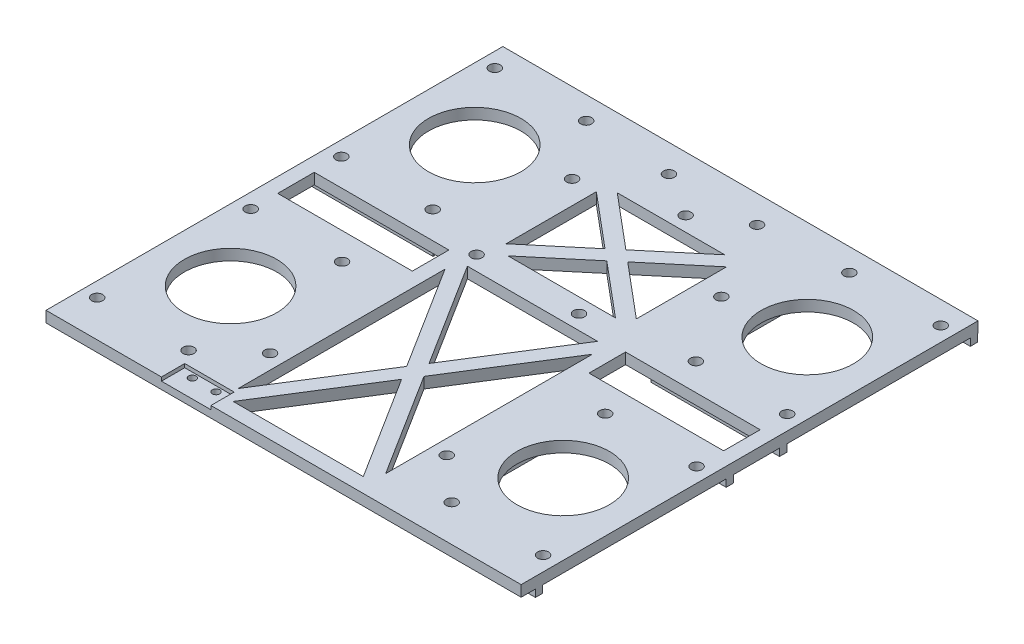
SolidWorks part; units mm, degrees
ref_plane "Front Plane" through (0, 0, 0) normal (0, 0, 1) x (1, 0, 0)
ref_plane "Top Plane" through (0, 0, 0) normal (0, 1, 0) x (1, 0, 0)
ref_plane "Right Plane" through (0, 0, 0) normal (1, 0, 0) x (0, 0, -1)
sketch "Sketch1" plane through (0, 0, 0) normal (0, 1, 0) x (1, 0, 0)
  line L1 (-65, 62.5) -> (65, 62.5)
  line L2 (-65, 62.5) -> (-65, -62.5)
  line L3 (-65, -62.5) -> (65, -62.5)
  line L4 (65, 62.5) -> (65, -62.5)
  line L5 (-65, 62.5) -> (65, -62.5) construction
  line L6 (-65, -62.5) -> (65, 62.5) construction
  point P0 (0, 0)
  dimension "D1" = 130
  dimension "D2" = 125
extrude "Boss-Extrude1" add sketch "Sketch1" along normal blind 5
sketch "Sketch2" plane through (0, 5, 0) normal (0, 1, 0) x (1, 0, 0)
  line L1 (-65, -62.5) -> (65, -62.5) construction
  line L2 (-65, 62.5) -> (-65, -62.5) construction
  circle A0 centre (-61, -52.5) radius 1.5
  circle A1 centre (-36, -52.5) radius 1.5
  circle A2 centre (-36, -10.5) radius 1.5
  circle A3 centre (-61, -10.5) radius 1.5
  circle A4 centre (-45.5, -31.5) radius 12.65
  dimension "D2" = 25.3
  dimension "D7" = 3
  dimension "D8" = 3
  dimension "D9" = 3
  dimension "D10" = 3
  dimension "D1" = 19.5
  dimension "D3" = 31
  dimension "D4" = 4
  dimension "D5" = 10
  dimension "D6" = 10
  dimension "D11" = 4
  dimension "D12" = 42
  dimension "D13" = 42
  dimension "D14" = 25
  dimension "D15" = 25
extrude "Cut-Extrude1" cut sketch "Sketch2" against normal blind 10
ref_plane "Plane1" through (0, 0, 0) normal (-1, 0, 0) x (0, 0, 1)
ref_plane "Plane2" through (0, 0, 0) normal (0, 0, 1) x (1, 0, 0)
mirror "Mirror3" about plane through (0, 0, 0) normal (-1, 0, 0) of "Cut-Extrude1"
sketch "Sketch4" plane through (0, 5, 0) normal (0, 1, 0) x (1, 0, 0)
  line L0 (0, 62.5) -> (0, 47.5) construction
  line L1 (65, 62.5) -> (-65, 62.5) construction
  line L2 (-12.0498, 55) -> (12.0498, 55) construction
  circle A0 centre (0, 47.5) radius 1.5
  circle A1 centre (12.0498, 55) radius 1.5
  circle A2 centre (-12.0498, 55) radius 1.5
  point P9 (0, 55)
  dimension "D2" = 3
  dimension "D3" = 3
  dimension "D4" = 3
  dimension "D1" = 15
  dimension "D5" = 24.0996
extrude "Cut-Extrude3" cut sketch "Sketch4" against normal blind 10
sketch "Sketch5" plane through (0, 0, 0) normal (0, -1, 0) x (1, 0, 0)
  line L0 (-58.15, 31.5) -> (-65, 31.5) construction
  line L1 (-65, -62.5) -> (-65, 62.5) construction
  line L2 (-65, 56.6) -> (-65, 6.4)
  line L3 (-65, 56.6) -> (-31.8, 56.6)
  line L4 (-31.8, 56.6) -> (-31.8, 6.4)
  line L5 (-31.8, 6.4) -> (-65, 6.4)
  line L6 (-65, 58.6) -> (-29.8, 58.6)
  line L7 (-29.8, 58.6) -> (-29.8, 4.4)
  line L8 (-29.8, 4.4) -> (-65, 4.4)
  line L9 (-65, 4.4) -> (-65, 6.4)
  line L10 (-65, 58.6) -> (-65, 56.6)
  circle A0 centre (-45.5, 31.5) radius 12.65 construction
  point P10 (-65, 31.5)
  line M39 (-65, 62.5) -> (-65, -62.5)
  dimension "D1" = 50.2
  dimension "D2" = 33.2
  dimension "D3" = 2
  dimension "D4" = 2
  dimension "D5" = 2
extrude "Boss-Extrude2" add sketch "Sketch5" along normal blind 2 contours L8 L7 L6 L3 L4 L5 M39 region at (-64.3537, 0, 57.6)
mirror "Mirror5" about plane through (0, 0, 0) normal (-1, 0, 0) of "Boss-Extrude2"
ref_plane "Plane3" through (0, 0, 0) normal (0, 0, 1) x (1, 0, 0)
ref_plane "Plane4" through (0, 0, -1.9) normal (0, 0, 1) x (1, 0, 0)
mirror "Mirror7" about plane through (0, 0, -1.9) normal (0, 0, 1) of "Mirror5", "Boss-Extrude2", "Mirror3"
ref_plane "Plane5" through (0, 0, 0) normal (0, -1, 0) x (-1, 0, 0)
sketch "Sketch10" plane through (0, 0, 0) normal (0, -1, 0) x (-1, 0, 0)
  circle A0 centre (-24.17, -42.03) radius 1.5
  circle A1 centre (24.17, -42.03) radius 1.5
  circle A2 centre (-8.73, 9.6) radius 1.5
  circle A3 centre (19.29, 9.6) radius 1.5
  circle A4 centre (-24.17, 33.11) radius 1.5
  circle A5 centre (24.17, 40.6) radius 1.5
  dimension "D1" = 3
  dimension "D6" = 3
  dimension "D7" = 3
  dimension "D10" = 3
  dimension "D11" = 3
  dimension "D12" = 3
extrude "Cut-Extrude8" cut sketch "Sketch10" against normal through all
sketch "Sketch11" plane through (0, 0, 0) normal (0, -1, 0) x (1, 0, 0)
  circle A0 centre (-12.0498, -55) radius 2.65
  circle A1 centre (0, -47.5) radius 2.65
  circle A2 centre (12.0498, -55) radius 2.65
  circle A3 centre (-24.17, -40.6) radius 2.65
  circle A4 centre (24.17, -33.11) radius 2.65
  circle A5 centre (8.73, -9.6) radius 2.65
  circle A6 centre (-19.29, -9.6) radius 2.65
  circle A7 centre (-24.17, 42.03) radius 2.65
  circle A8 centre (24.17, 42.03) radius 2.65
  circle A9 centre (-61, -14.3) radius 2.65
  circle A10 centre (-36, -14.3) radius 2.65
  circle A11 centre (-61, -56.3) radius 2.65
  circle A12 centre (-36, -56.3) radius 2.65
  circle A13 centre (36, -56.3) radius 2.65
  circle A14 centre (61, -56.3) radius 2.65
  circle A15 centre (36, -14.3) radius 2.65
  circle A16 centre (61, -14.3) radius 2.65
  circle A17 centre (36, 10.5) radius 2.65
  circle A18 centre (61, 10.5) radius 2.65
  circle A19 centre (61, 52.5) radius 2.65
  circle A20 centre (36, 52.5) radius 2.65
  circle A21 centre (-36, 52.5) radius 2.65
  circle A22 centre (-36, 10.5) radius 2.65
  circle A23 centre (-61, 10.5) radius 2.65
  circle A24 centre (-61, 52.5) radius 2.65
  dimension "D1" = 5.3
  dimension "D2" = 5.3
  dimension "D3" = 5.3
  dimension "D4" = 5.3
  dimension "D5" = 5.3
  dimension "D6" = 5.3
  dimension "D7" = 5.3
  dimension "D8" = 5.3
  dimension "D9" = 5.3
  dimension "D10" = 5.3
  dimension "D11" = 5.3
  dimension "D12" = 5.3
  dimension "D13" = 5.3
  dimension "D14" = 5.3
  dimension "D15" = 5.3
  dimension "D16" = 5.3
  dimension "D17" = 5.3
  dimension "D18" = 5.3
  dimension "D19" = 5.3
  dimension "D20" = 5.3
  dimension "D21" = 5.3
  dimension "D22" = 5.3
  dimension "D23" = 5.3
  dimension "D24" = 5.3
  dimension "D25" = 5.3
extrude "Cut-Extrude9" cut sketch "Sketch11" against normal blind 0.5
sketch "Sketch12" plane through (0, 5, 0) normal (0, 1, 0) x (1, 0, 0)
  line L0 (-65, -62.5) -> (65, -62.5) construction
  line L1 (-20.17, 5.6) -> (20.17, 5.6)
  line L2 (-20.17, 5.6) -> (-20.17, -58.5)
  line L3 (-20.17, -58.5) -> (20.17, -58.5)
  line L4 (20.17, 5.6) -> (20.17, -58.5)
  line L5 (-20.17, 5.6) -> (20.17, -58.5) construction
  line L6 (-20.17, -58.5) -> (20.17, 5.6) construction
  line L7 (-17.8069, 5.6) -> (0, -22.6951)
  line L8 (20.17, -54.7451) -> (2.3631, -26.45)
  line L9 (2.3631, -26.45) -> (20.17, 1.8451)
  line L10 (0, -22.6951) -> (17.8069, 5.6)
  line L11 (-20.17, 1.8451) -> (-2.3631, -26.45)
  line L12 (-2.3631, -26.45) -> (-20.17, -54.7451)
  line L13 (-17.8069, -58.5) -> (0, -30.2049)
  line L14 (0, -30.2049) -> (17.8069, -58.5)
  circle A0 centre (-19.29, 9.6) radius 1.5 construction
  circle A1 centre (-24.17, -42.03) radius 1.5 construction
  circle A2 centre (24.17, -42.03) radius 1.5 construction
  dimension "D2" = 4
  dimension "D3" = 4
  dimension "D1" = 4
  dimension "D4" = 4
  dimension "D5" = 2
  dimension "D6" = 2
  dimension "D7" = 2
  dimension "D8" = 2
extrude "Cut-Extrude10" cut sketch "Sketch12" against normal through all contours L12 L11 L2 | L7 L10 L1 | L9 L8 L4 | L14 L13 L3 region at (0, 5, 3.8317) region at (-14.2344, 5, 26.45) region at (14.2344, 5, 26.45) region at (0, 5, 49.0683)
sketch "Sketch13" plane through (0, 5, 0) normal (0, 1, 0) x (1, 0, 0)
  line L0 (-61, 14.3) -> (-61, -10.5) construction
  line L1 (-61, 1.9) -> (-61, -3.1)
  line L2 (-61, -3.1) -> (-24.17, -3.1)
  line L3 (-24.17, -3.1) -> (-24.17, 6.9)
  line L4 (-24.17, 6.9) -> (-61, 6.9)
  line L5 (-61, 6.9) -> (-61, 1.9)
  line L6 (-20.17, 1.8451) -> (-20.17, -54.7451) construction
  dimension "D1" = 10
  dimension "D2" = 5
  dimension "D3" = 4
extrude "Cut-Extrude11" cut sketch "Sketch13" against normal through all
mirror "Mirror9" about plane through (0, 0, 0) normal (-1, 0, 0) of "Cut-Extrude11"
sketch "Sketch14" plane through (0, 5, 0) normal (0, 1, 0) x (1, 0, 0)
  line L0 (-17.8069, 43.5) -> (17.8069, 13.6) construction
  line L1 (-17.8069, 43.5) -> (17.8069, 43.5)
  line L2 (-17.8069, 43.5) -> (-17.8069, 13.6)
  line L3 (-17.8069, 13.6) -> (17.8069, 13.6)
  line L4 (17.8069, 43.5) -> (17.8069, 13.6)
  line L5 (-17.8069, 13.6) -> (17.8069, 43.5) construction
  line L6 (-17.8069, 40.8886) -> (-3.1104, 28.55)
  line L7 (-3.1104, 28.55) -> (-17.8069, 16.2114)
  line L8 (-14.6965, 13.6) -> (0, 25.9386)
  line L9 (0, 25.9386) -> (14.6965, 13.6)
  line L10 (17.8069, 16.2114) -> (3.1104, 28.55)
  line L11 (3.1104, 28.55) -> (17.8069, 40.8886)
  line L12 (14.6965, 43.5) -> (0, 31.1614)
  line L13 (0, 31.1614) -> (-14.6965, 43.5)
  circle A0 centre (0, 47.5) radius 1.5 construction
  circle A1 centre (8.73, 9.6) radius 1.5 construction
  dimension "D1" = 4
  dimension "D2" = 4
  dimension "D3" = 2
  dimension "D4" = 2
  dimension "D5" = 2
  dimension "D6" = 2
  dimension "D7" = 2
  dimension "D8" = 2
  dimension "D9" = 2
  dimension "D10" = 2
extrude "Cut-Extrude12" cut sketch "Sketch14" against normal through all contours L7 L6 L2 | L13 L12 L1 | L11 L10 L4 | L9 L8 L3 region at (0, 5, -39.3871) region at (-12.9081, 5, -28.55) region at (12.9081, 5, -28.55) region at (0, 5, -17.7129)
sketch "Sketch15" plane through (0, 5, 0) normal (0, 1, 0) x (1, 0, 0)
  line L1 (-63.5, 58.8) -> (-58.5, 58.8)
  line L2 (-63.5, 58.8) -> (-63.5, 53.8)
  line L3 (-63.5, 53.8) -> (-58.5, 53.8)
  line L4 (65, -62.5) -> (65, 62.5)
  line L5 (65, 62.5) -> (-65, 62.5)
  line L6 (-65, 62.5) -> (-65, -62.5)
  line L7 (-65, -62.5) -> (65, -62.5)
  line L8 (65, -62.5) -> (65, 62.5)
  line L9 (65, 62.5) -> (-65, 62.5)
  line L10 (-65, 62.5) -> (-65, -62.5)
  line L11 (-65, -62.5) -> (65, -62.5)
  line L12 (-58.5, 58.8) -> (-58.5, 53.8)
  line L13 (-63.5, 58.8) -> (-58.5, 53.8) construction
  line L14 (-63.5, 53.8) -> (-58.5, 58.8) construction
  line L15 (-38.5, 58.8) -> (-33.5, 58.8)
  line L16 (-38.5, 58.8) -> (-38.5, 53.8)
  line L17 (-38.5, 53.8) -> (-33.5, 53.8)
  line L18 (-33.5, 58.8) -> (-33.5, 53.8)
  line L19 (-38.5, 58.8) -> (-33.5, 53.8) construction
  line L20 (-38.5, 53.8) -> (-33.5, 58.8) construction
  line L21 (-14.5498, 57.5) -> (-9.5498, 57.5)
  line L22 (-14.5498, 57.5) -> (-14.5498, 52.5)
  line L23 (-14.5498, 52.5) -> (-9.5498, 52.5)
  line L24 (-9.5498, 57.5) -> (-9.5498, 52.5)
  line L25 (-14.5498, 57.5) -> (-9.5498, 52.5) construction
  line L26 (-14.5498, 52.5) -> (-9.5498, 57.5) construction
  line L27 (-2.5, 50) -> (2.5, 50)
  line L28 (-2.5, 50) -> (-2.5, 45)
  line L29 (-2.5, 45) -> (2.5, 45)
  line L30 (2.5, 50) -> (2.5, 45)
  line L31 (-2.5, 50) -> (2.5, 45) construction
  line L32 (-2.5, 45) -> (2.5, 50) construction
  line L33 (9.5498, 57.5) -> (14.5498, 57.5)
  line L34 (9.5498, 57.5) -> (9.5498, 52.5)
  line L35 (9.5498, 52.5) -> (14.5498, 52.5)
  line L36 (14.5498, 57.5) -> (14.5498, 52.5)
  line L37 (9.5498, 57.5) -> (14.5498, 52.5) construction
  line L38 (9.5498, 52.5) -> (14.5498, 57.5) construction
  line L39 (33.5, 58.8) -> (38.5, 58.8)
  line L40 (33.5, 58.8) -> (33.5, 53.8)
  line L41 (33.5, 53.8) -> (38.5, 53.8)
  line L42 (38.5, 58.8) -> (38.5, 53.8)
  line L43 (33.5, 58.8) -> (38.5, 53.8) construction
  line L44 (33.5, 53.8) -> (38.5, 58.8) construction
  line L45 (63.5, 58.8) -> (58.5, 58.8)
  line L46 (63.5, 58.8) -> (63.5, 53.8)
  line L47 (63.5, 53.8) -> (58.5, 53.8)
  line L48 (58.5, 58.8) -> (58.5, 53.8)
  line L49 (63.5, 58.8) -> (58.5, 53.8) construction
  line L50 (63.5, 53.8) -> (58.5, 58.8) construction
  line L51 (33.5, 16.8) -> (38.5, 16.8)
  line L52 (33.5, 16.8) -> (33.5, 11.8)
  line L53 (33.5, 11.8) -> (38.5, 11.8)
  line L54 (38.5, 16.8) -> (38.5, 11.8)
  line L55 (33.5, 16.8) -> (38.5, 11.8) construction
  line L56 (33.5, 11.8) -> (38.5, 16.8) construction
  line L57 (63.5, 16.8) -> (58.5, 16.8)
  line L58 (63.5, 16.8) -> (63.5, 11.8)
  line L59 (63.5, 11.8) -> (58.5, 11.8)
  line L60 (58.5, 16.8) -> (58.5, 11.8)
  line L61 (63.5, 16.8) -> (58.5, 11.8) construction
  line L62 (63.5, 11.8) -> (58.5, 16.8) construction
  line L63 (21.67, 35.61) -> (26.67, 35.61)
  line L64 (21.67, 35.61) -> (21.67, 30.61)
  line L65 (21.67, 30.61) -> (26.67, 30.61)
  line L66 (26.67, 35.61) -> (26.67, 30.61)
  line L67 (21.67, 35.61) -> (26.67, 30.61) construction
  line L68 (21.67, 30.61) -> (26.67, 35.61) construction
  line L69 (33.5, -8) -> (38.5, -8)
  line L70 (33.5, -8) -> (33.5, -13)
  line L71 (33.5, -13) -> (38.5, -13)
  line L72 (38.5, -8) -> (38.5, -13)
  line L73 (33.5, -8) -> (38.5, -13) construction
  line L74 (33.5, -13) -> (38.5, -8) construction
  line L75 (63.5, -8) -> (58.5, -8)
  line L76 (63.5, -8) -> (63.5, -13)
  line L77 (63.5, -13) -> (58.5, -13)
  line L78 (58.5, -8) -> (58.5, -13)
  line L79 (63.5, -8) -> (58.5, -13) construction
  line L80 (63.5, -13) -> (58.5, -8) construction
  line L81 (21.67, -39.53) -> (26.67, -39.53)
  line L82 (21.67, -39.53) -> (21.67, -44.53)
  line L83 (21.67, -44.53) -> (26.67, -44.53)
  line L84 (26.67, -39.53) -> (26.67, -44.53)
  line L85 (21.67, -39.53) -> (26.67, -44.53) construction
  line L86 (21.67, -44.53) -> (26.67, -39.53) construction
  line L87 (38.5, -50) -> (33.5, -50)
  line L88 (38.5, -50) -> (38.5, -55)
  line L89 (38.5, -55) -> (33.5, -55)
  line L90 (33.5, -50) -> (33.5, -55)
  line L91 (38.5, -50) -> (33.5, -55) construction
  line L92 (38.5, -55) -> (33.5, -50) construction
  line L93 (63.5, -50) -> (58.5, -50)
  line L94 (63.5, -50) -> (63.5, -55)
  line L95 (63.5, -55) -> (58.5, -55)
  line L96 (58.5, -50) -> (58.5, -55)
  line L97 (63.5, -50) -> (58.5, -55) construction
  line L98 (63.5, -55) -> (58.5, -50) construction
  line L99 (-26.67, -39.53) -> (-21.67, -39.53)
  line L100 (-26.67, -39.53) -> (-26.67, -44.53)
  line L101 (-26.67, -44.53) -> (-21.67, -44.53)
  line L102 (-21.67, -39.53) -> (-21.67, -44.53)
  line L103 (-26.67, -39.53) -> (-21.67, -44.53) construction
  line L104 (-26.67, -44.53) -> (-21.67, -39.53) construction
  line L105 (-38.5, -50) -> (-33.5, -50)
  line L106 (-38.5, -50) -> (-38.5, -55)
  line L107 (-38.5, -55) -> (-33.5, -55)
  line L108 (-33.5, -50) -> (-33.5, -55)
  line L109 (-38.5, -50) -> (-33.5, -55) construction
  line L110 (-38.5, -55) -> (-33.5, -50) construction
  line L111 (-38.5, -8) -> (-33.5, -8)
  line L112 (-38.5, -8) -> (-38.5, -13)
  line L113 (-38.5, -13) -> (-33.5, -13)
  line L114 (-33.5, -8) -> (-33.5, -13)
  line L115 (-38.5, -8) -> (-33.5, -13) construction
  line L116 (-38.5, -13) -> (-33.5, -8) construction
  line L117 (6.23, 12.1) -> (11.23, 12.1)
  line L118 (6.23, 12.1) -> (6.23, 7.1)
  line L119 (6.23, 7.1) -> (11.23, 7.1)
  line L120 (11.23, 12.1) -> (11.23, 7.1)
  line L121 (6.23, 12.1) -> (11.23, 7.1) construction
  line L122 (6.23, 7.1) -> (11.23, 12.1) construction
  line L123 (-21.79, 12.1) -> (-16.79, 12.1)
  line L124 (-21.79, 12.1) -> (-21.79, 7.1)
  line L125 (-21.79, 7.1) -> (-16.79, 7.1)
  line L126 (-16.79, 12.1) -> (-16.79, 7.1)
  line L127 (-21.79, 12.1) -> (-16.79, 7.1) construction
  line L128 (-21.79, 7.1) -> (-16.79, 12.1) construction
  line L129 (-26.67, 43.1) -> (-21.67, 43.1)
  line L130 (-26.67, 43.1) -> (-26.67, 38.1)
  line L131 (-26.67, 38.1) -> (-21.67, 38.1)
  line L132 (-21.67, 43.1) -> (-21.67, 38.1)
  line L133 (-26.67, 43.1) -> (-21.67, 38.1) construction
  line L134 (-26.67, 38.1) -> (-21.67, 43.1) construction
  line L135 (-63.5, 16.8) -> (-58.5, 16.8)
  line L136 (-63.5, 16.8) -> (-63.5, 11.8)
  line L137 (-63.5, 11.8) -> (-58.5, 11.8)
  line L138 (-58.5, 16.8) -> (-58.5, 11.8)
  line L139 (-63.5, 16.8) -> (-58.5, 11.8) construction
  line L140 (-63.5, 11.8) -> (-58.5, 16.8) construction
  line L141 (-38.5, 16.8) -> (-33.5, 16.8)
  line L142 (-38.5, 16.8) -> (-38.5, 11.8)
  line L143 (-38.5, 11.8) -> (-33.5, 11.8)
  line L144 (-33.5, 16.8) -> (-33.5, 11.8)
  line L145 (-38.5, 16.8) -> (-33.5, 11.8) construction
  line L146 (-38.5, 11.8) -> (-33.5, 16.8) construction
  line L147 (-63.5, -8) -> (-58.5, -8)
  line L148 (-63.5, -8) -> (-63.5, -13)
  line L149 (-63.5, -13) -> (-58.5, -13)
  line L150 (-58.5, -8) -> (-58.5, -13)
  line L151 (-63.5, -8) -> (-58.5, -13) construction
  line L152 (-63.5, -13) -> (-58.5, -8) construction
  line L153 (-63.5, -50) -> (-58.5, -50)
  line L154 (-63.5, -50) -> (-63.5, -55)
  line L155 (-63.5, -55) -> (-58.5, -55)
  line L156 (-58.5, -50) -> (-58.5, -55)
  line L157 (-63.5, -50) -> (-58.5, -55) construction
  line L158 (-63.5, -55) -> (-58.5, -50) construction
  circle A0 centre (-61, 56.3) radius 1.5 construction
  circle A1 centre (-36, 56.3) radius 1.5 construction
  circle A2 centre (-12.0498, 55) radius 1.5 construction
  circle A3 centre (0, 47.5) radius 1.5 construction
  circle A4 centre (12.0498, 55) radius 1.5 construction
  circle A5 centre (36, 56.3) radius 1.5 construction
  circle A6 centre (61, 56.3) radius 1.5 construction
  circle A7 centre (24.17, 33.11) radius 1.5 construction
  circle A8 centre (36, 14.3) radius 1.5 construction
  circle A9 centre (61, 14.3) radius 1.5 construction
  circle A10 centre (-24.17, 40.6) radius 1.5 construction
  circle A11 centre (-61, 14.3) radius 1.5 construction
  circle A12 centre (-36, 14.3) radius 1.5 construction
  circle A13 centre (-19.29, 9.6) radius 1.5 construction
  circle A14 centre (8.73, 9.6) radius 1.5 construction
  circle A15 centre (-61, -10.5) radius 1.5 construction
  circle A16 centre (-36, -10.5) radius 1.5 construction
  circle A17 centre (36, -10.5) radius 1.5 construction
  circle A18 centre (61, -10.5) radius 1.5 construction
  circle A19 centre (61, -52.5) radius 1.5 construction
  circle A20 centre (36, -52.5) radius 1.5 construction
  circle A21 centre (24.17, -42.03) radius 1.5 construction
  circle A22 centre (-24.17, -42.03) radius 1.5 construction
  circle A23 centre (-36, -52.5) radius 1.5 construction
  circle A24 centre (-61, -52.5) radius 1.5 construction
  point P2 (-61, 56.3)
  point P12 (-36, 56.3)
  point P20 (-12.0498, 55)
  point P26 (0, 47.5)
  point P32 (12.0498, 55)
  point P38 (36, 56.3)
  point P44 (61, 56.3)
  point P50 (36, 14.3)
  point P56 (61, 14.3)
  point P62 (24.17, 33.11)
  point P84 (36, -10.5)
  point P90 (61, -10.5)
  point P96 (24.17, -42.03)
  point P102 (36, -52.5)
  point P108 (61, -52.5)
  point P114 (-24.17, -42.03)
  point P120 (-36, -52.5)
  point P126 (-36, -10.5)
  point P132 (8.73, 9.6)
  point P138 (-19.29, 9.6)
  point P144 (-24.17, 40.6)
  point P150 (-61, 14.3)
  point P156 (-36, 14.3)
  point P162 (-61, -10.5)
  point P168 (-61, -52.5)
  dimension "D2" = 2.5
  dimension "D3" = 2.5
  dimension "D4" = 2.5
  dimension "D5" = 2.5
  dimension "D6" = 2.5
  dimension "D7" = 2.5
  dimension "D8" = 2.5
  dimension "D9" = 2.5
  dimension "D10" = 2.5
  dimension "D11" = 2.5
  dimension "D12" = 2.5
  dimension "D13" = 2.5
  dimension "D15" = 2.5
  dimension "D16" = 2.5
  dimension "D17" = 2.5
  dimension "D18" = 2.5
  dimension "D19" = 2.5
  dimension "D20" = 2.5
  dimension "D21" = 2.5
  dimension "D22" = 2.5
  dimension "D23" = 2.5
  dimension "D24" = 2.5
  dimension "D25" = 2.5
  dimension "D26" = 2.5
  dimension "D27" = 2.5
  dimension "D28" = 2.5
  dimension "D29" = 2.5
  dimension "D30" = 2.5
  dimension "D31" = 2.5
  dimension "D32" = 2.5
  dimension "D33" = 2.5
  dimension "D34" = 2.5
  dimension "D35" = 2.5
  dimension "D36" = 2.5
  dimension "D37" = 2.5
  dimension "D38" = 2.5
  dimension "D39" = 2.5
  dimension "D40" = 2.5
  dimension "D41" = 2.5
  dimension "D42" = 2.5
  dimension "D43" = 2.5
  dimension "D44" = 2.5
  dimension "D45" = 2.5
  dimension "D46" = 2.5
  dimension "D47" = 2.5
  dimension "D48" = 2.5
  dimension "D49" = 2.5
  dimension "D14" = 2.5
  dimension "D1" = 0
extrude "Cut-Extrude14" cut sketch "Sketch15" against normal blind 2
ref_plane "Plane6" through (0, 13, 0) normal (0, 1, 0) x (1, 0, 0)
sketch "Sketch17" plane through (0, 13, 0) normal (0, 1, 0) x (1, 0, 0)
  line L1 (-68.0587, 64.2777) -> (69.5711, 64.2777)
  line L2 (-68.0587, 64.2777) -> (-68.0587, -66.7984)
  line L3 (-68.0587, -66.7984) -> (69.5711, -66.7984)
  line L4 (69.5711, 64.2777) -> (69.5711, -66.7984)
extrude "Cut-Extrude15" cut sketch "Sketch17" against normal blind 2 from surface starting at face at (-61, 5, -15.8)
sketch "Sketch18" plane through (0, 3, 0) normal (0, 1, 0) x (1, 0, 0)
  line L0 (-65, -62.5) -> (65, -62.5) construction
  line L1 (-33.412, -56.1297) -> (-19.8846, -56.1297)
  line L2 (-33.412, -56.1297) -> (-33.412, -62.5)
  line L3 (-33.412, -62.5) -> (-19.8846, -62.5)
  line L4 (-19.8846, -56.1297) -> (-19.8846, -62.5)
extrude "Cut-Extrude16" cut sketch "Sketch18" against normal blind 1
sketch "Sketch19" plane through (0, 2, 0) normal (0, 1, 0) x (1, 0, 0)
  circle A0 centre (-23.4201, -57.55) radius 1
  circle A1 centre (-29.9201, -57.55) radius 1
extrude "Cut-Extrude17" cut sketch "Sketch19" against normal blind 5
sketch "Sketch20" plane through (0, 0, 0) normal (0, -1, 0) x (1, 0, 0)
  line L1 (-32.8112, 59.7055) -> (-26.1535, 59.7055)
  line L2 (-32.8112, 59.7055) -> (-32.8112, 55.2822)
  line L3 (-32.8112, 55.2822) -> (-26.1535, 55.2822)
  line L4 (-26.1535, 59.7055) -> (-26.1535, 55.2822)
extrude "Cut-Extrude18" cut sketch "Sketch20" along normal up to surface (2 mm away) up to face at (-44.392, -2, 36.71)
